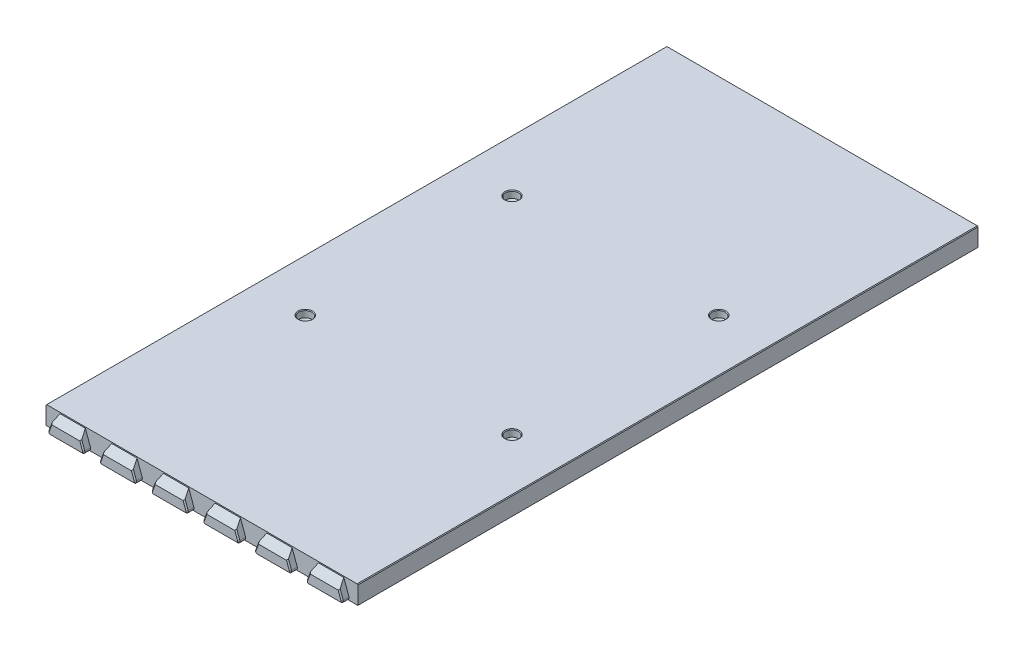
SolidWorks part; units mm, degrees
ref_plane "Front Plane" through (0, 0, 0) normal (0, 0, 1) x (1, 0, 0)
ref_plane "Top Plane" through (0, 0, 0) normal (0, 1, 0) x (1, 0, 0)
ref_plane "Right Plane" through (0, 0, 0) normal (1, 0, 0) x (0, 0, -1)
sketch "Sketch1" plane through (0, 0, 0) normal (0, 0, 1) x (1, 0, 0)
  line L0 (0, 0) -> (0, 8) construction
  line L1 (-67.875, 0) -> (0, 0) construction
  line L2 (-67.875, 0) -> (-67.875, 8)
  line L3 (-67.875, 8) -> (67.875, 8)
  line L5 (-67.875, 0) -> (-65.875, 0)
  line L6 (-65.875, 0) -> (-65.875, 6)
  line L7 (-65.875, 6) -> (65.875, 6)
  line L9 (65.875, 0) -> (65.875, 6)
  line L10 (67.875, 0) -> (65.875, 0)
  line L11 (67.875, 0) -> (67.875, 8)
  point P8 (0, 6)
  dimension "D2" = 6
  dimension "D1" = 67.875
  dimension "D3" = 2
  dimension "D4" = 2
extrude "Boss-Extrude1" add sketch "Sketch1" against normal blind 135
sketch "Sketch7" plane through (0, 0, 0) normal (0, 0, 1) x (1, 0, 0)
  line L2 (-65.875, 0) -> (65.875, 0)
  line L13 (-65.875, 0) -> (-65.875, 6)
  line L15 (-65.875, 6) -> (65.875, 6)
  line L16 (65.875, 0) -> (65.875, 6)
  line M3 (-65.875, 0) -> (-65.875, 6)
  line M4 (-65.875, 6) -> (65.875, 6)
  line M5 (65.875, 6) -> (65.875, 0)
extrude "Boss-Extrude7" add sketch "Sketch7" against normal blind 1 contours M4 M3 | M5 region at (0, 3, 0)
sketch "Sketch2" plane through (0, 0, 0) normal (0, 0, 1) x (1, 0, 0)
  line L14 (50.9118, 8) -> (48, 0)
  line L15 (67.875, 8) -> (-67.875, 8) construction
  line L16 (-67.875, 0) -> (67.875, 0) construction
  line L17 (48, 0) -> (64.5, 0)
  line L18 (50.9118, 8) -> (61.5882, 8)
  line L19 (-67.875, 0) -> (67.875, 0) construction
  line L21 (61.5882, 8) -> (64.5, 0)
  line L24 (45, 0) -> (45, 8) construction
  line L27 (28.4118, 8) -> (25.5, 0)
  line L28 (28.4118, 8) -> (39.0882, 8)
  line L29 (25.5, 0) -> (42, 0)
  line L30 (39.0882, 8) -> (42, 0)
  line L31 (5.9118, 8) -> (3, 0)
  line L32 (5.9118, 8) -> (16.5882, 8)
  line L33 (3, 0) -> (19.5, 0)
  line L34 (16.5882, 8) -> (19.5, 0)
  line L35 (-16.5882, 8) -> (-19.5, 0)
  line L36 (-16.5882, 8) -> (-5.9118, 8)
  line L37 (-19.5, 0) -> (-3, 0)
  line L38 (-5.9118, 8) -> (-3, 0)
  line L39 (50.9118, 8) -> (28.4118, 8) construction
  line L40 (67.5, 8) -> (67.5, 0) construction
  line L41 (67.875, 0) -> (67.875, 8) construction
  line L42 (-67.5, 8) -> (-67.5, 0) construction
  line L43 (-67.875, 8) -> (-67.875, 0) construction
  line L44 (-39.0882, 8) -> (-42, 0)
  line L45 (-39.0882, 8) -> (-28.4118, 8)
  line L46 (-42, 0) -> (-25.5, 0)
  line L47 (-28.4118, 8) -> (-25.5, 0)
  line L48 (-61.5882, 8) -> (-64.5, 0)
  line L49 (-61.5882, 8) -> (-50.9118, 8)
  line L50 (-64.5, 0) -> (-48, 0)
  line L51 (-50.9118, 8) -> (-48, 0)
  point P22 (56.25, 8)
  point P23 (33.75, 8)
  dimension "D1" = 70
  dimension "D2" = 0.375
  dimension "D3" = 3
  dimension "D4" = 3
  dimension "D5" = 70
  dimension "D7" = 22.5
  dimension "D8" = 22.5
  dimension "D9" = 0.375
  dimension "D10" = 48
  dimension "D11" = 8
  dimension "D6" = 6
extrude "Boss-Extrude4" add sketch "Sketch2" along normal blind 3
sketch "Sketch8" plane through (0, 0, 0) normal (0, -1, 0) x (1, 0, 0)
  line L0 (-67.875, -22.5) -> (67.875, -22.5) construction
  line L1 (-66.35, -20.2583) -> (-62.65, -21.605)
  line L2 (67.875, -135) -> (67.875, 0) construction
  line L3 (-67.875, 0) -> (-64.5, 0) construction
  line L4 (-66.5, -24.9559) -> (-66.5, -20.0441) construction
  line L5 (-66.5, -20.0441) -> (-62.5, -21.5) construction
  line L6 (-62.5, -21.5) -> (-62.5, -23.5) construction
  line L7 (-66.5, -135) -> (-66.5, -132.5441) construction
  line L8 (-66.5, -132.5441) -> (-62.5, -134) construction
  line L9 (-62.5, -134) -> (-62.5, -135) construction
  line L10 (-65.875, -135) -> (65.875, -135) construction
  line L11 (-62.5, -135) -> (-66.5, -135) construction
  line L12 (-66.5, -24.9559) -> (-62.5, -23.5) construction
  line L13 (0, -135) -> (0, 0) construction
  line L22 (-62.65, -21.605) -> (-62.65, -23.395)
  line L23 (-67.875, -135) -> (-67.875, 0) construction
  line L28 (-67.875, -135) -> (-65.875, -135) construction
  line L33 (-66.35, -24.7417) -> (-62.65, -23.395)
  line L34 (-66.35, -24.7417) -> (-66.35, -20.2583)
  line L35 (-66.35, -132.7583) -> (-62.65, -134.105)
  line L36 (-62.65, -134.105) -> (-62.65, -134.85)
  line L37 (-62.65, -134.85) -> (-66.35, -134.85) construction
  line L38 (-66.35, -134.85) -> (-66.35, -132.7583)
  line L39 (-66.35, -134.85) -> (-66.35, -135)
  line L40 (-66.35, -135) -> (-62.65, -135)
  line L41 (-62.65, -135) -> (-62.65, -134.85)
  line L42 (66.35, -24.7417) -> (66.35, -20.2583)
  line L43 (66.35, -24.7417) -> (62.65, -23.395)
  line L44 (62.65, -21.605) -> (62.65, -23.395)
  line L45 (66.35, -20.2583) -> (62.65, -21.605)
  line L46 (66.35, -135) -> (62.65, -135)
  line L47 (66.35, -134.85) -> (66.35, -135)
  line L48 (66.35, -134.85) -> (66.35, -132.7583)
  line L49 (66.35, -132.7583) -> (62.65, -134.105)
  line L50 (62.65, -134.105) -> (62.65, -134.85)
  line L51 (62.65, -135) -> (62.65, -134.85)
  point P19 (-62.5, -22.5)
  dimension "D1" = 22.5
  dimension "D2" = 0.15
  dimension "D3" = 70
  dimension "D4" = 4
  dimension "D5" = 1.375
  dimension "D6" = 4
  dimension "D7" = 70
  dimension "D8" = 1
  dimension "D9" = 1
  dimension "D10" = 0.15
extrude "Boss-Extrude8" add sketch "Sketch8" against normal up to next and the other way blind 2
chamfer "Chamfer4" distance 0.5 angle 45 14 edges at (-64.5, -2, -133.4317) (-62.65, -2, -134.5525) (-66.35, -2, -133.8792) (62.65, -2, -22.5) (64.5, -2, -20.9317) (66.35, -2, -22.5) (64.5, -2, -24.0683) (-64.5, -2, -20.9317) (-62.65, -2, -22.5) (-64.5, -2, -24.0683) (-66.35, -2, -22.5) (62.65, -2, -134.5525) (64.5, -2, -133.4317) (66.35, -2, -133.8792)
fillet "Fillet4" radius 1 12 edges at (64.5, 0, 1.5) (48, 0, 1.5) (42, 0, 1.5) (25.5, 0, 1.5) (19.5, 0, 1.5) (3, 0, 1.5) (-3, 0, 1.5) (-19.5, 0, 1.5) (-25.5, 0, 1.5) (-42, 0, 1.5) (-48, 0, 1.5) (-64.5, 0, 1.5)
chamfer "Chamfer6" distance 0.5 angle 45 30 edges at (49.7001, 4.671, 3) (62.7999, 4.671, 3) (56.25, 0, 3) (-17.7999, 4.671, 3) (-11.25, 0, 3) (-4.7001, 4.671, 3) (4.7001, 4.671, 3) (11.25, 0, 3) (17.7999, 4.671, 3) (27.2001, 4.671, 3) (40.2999, 4.671, 3) (33.75, 0, 3) (-40.2999, 4.671, 3) (-27.2001, 4.671, 3) (-33.75, 0, 3) (-62.7999, 4.671, 3) (-49.7001, 4.671, 3) (-56.25, 0, 3) (-63.891, 0.4264, 3) (-48.609, 0.4264, 3) (-41.391, 0.4264, 3) (-26.109, 0.4264, 3) (-18.891, 0.4264, 3) (-3.609, 0.4264, 3) (3.609, 0.4264, 3) (18.891, 0.4264, 3) (26.109, 0.4264, 3) (41.391, 0.4264, 3) (48.609, 0.4264, 3) (63.891, 0.4264, 3)
fillet "Fillet2" radius 2 23 edges at (0, 6, -1) (-65.875, 3, -1) (65.875, 6, -10.7156) (65.875, 3, -1) (-65.875, 6, -10.7156) (62.65, 6, -22.5) (64.2625, 6, -21.0181) (65.875, 3, -20.4312) (65.875, 3, -24.5688) (64.2625, 6, -23.9819) (65.875, 6, -78.75) (65.875, 3, -132.9312) (64.2625, 6, -133.5181) (62.65, 6, -134.5525) (-62.65, 6, -134.5525) (-64.2625, 6, -133.5181) (-65.875, 3, -132.9312) (-65.875, 3, -20.4312) (-64.2625, 6, -21.0181) (-62.65, 6, -22.5) (-64.2625, 6, -23.9819) (-65.875, 6, -78.75) (-65.875, 3, -24.5688)
mirror "Mirror2" about plane through (0, 0, -135) normal (0, 0, 1) of "Fillet4", "Boss-Extrude1", "Boss-Extrude7", "Boss-Extrude4", "Boss-Extrude8", "Chamfer4", "Fillet2", "Chamfer6"
sketch "Sketch9" plane through (0, 0, 0) normal (0, 1, 0) x (1, 0, 0)
  line L16 (0, 135) -> (0, 0) construction
  line L17 (-67.875, 135) -> (67.875, 135) construction
  line L20 (67.875, 270) -> (67.875, 0) construction
  line L21 (-67.875, 270) -> (-67.875, 0) construction
  circle A0 centre (-45, 90) radius 5
  circle A4 centre (45, 90) radius 5
  circle A5 centre (45, 180) radius 5
  circle A6 centre (-45, 180) radius 5
  point P23 (0, 135)
  point P24 (0, 135)
  dimension "D3" = 10
  dimension "D1" = 45
  dimension "D2" = 45
extrude "Boss-Extrude9" add sketch "Sketch9" along normal up to next
fillet "Fillet3" radius 3 4 edges at (-45, 6, -95) (45, 6, -185) (-45, 6, -185) (45, 6, -95)
sketch "Sketch10" plane through (0, 0, 0) normal (0, 1, 0) x (1, 0, 0)
  circle A0 centre (-45, 180) radius 1.85
  circle A1 centre (-45, 90) radius 1.85
  circle A2 centre (45, 90) radius 1.85
  circle A3 centre (45, 180) radius 1.85
  dimension "D1" = 3.7
extrude "Cut-Extrude2" cut sketch "Sketch10" along normal through all
sketch "Sketch11" plane through (0, 8, 0) normal (0, 1, 0) x (1, 0, 0)
  circle A0 centre (-45, 180) radius 2.85
  circle A1 centre (45, 180) radius 2.85
  circle A2 centre (45, 90) radius 2.85
  circle A3 centre (-45, 90) radius 2.85
  dimension "D1" = 5.7
extrude "Cut-Extrude3" cut sketch "Sketch11" against normal blind 3
chamfer "Chamfer7" distance 1 angle 45 4 edges at (45, 5, -178.15) (-45, 5, -178.15) (45, 5, -88.15) (-45, 5, -88.15)
sketch "Sketch12" plane through (0, 0, 0) normal (1, 0, 0) x (0, 0, -1)
  line L0 (0, 7.5) -> (-3, 4.5)
  line L1 (-3, 1.171) -> (-3, 8) construction
  line L2 (-3, 4.5) -> (-3, 7.5)
  line L3 (-3, 7.5) -> (0, 7.5) construction
  line L4 (135, 8) -> (135, 0) construction
  line L5 (270, 8) -> (0, 8) construction
  line L6 (270, 0) -> (0, 0) construction
  line L10 (0, 0) -> (0, 8) construction
  line L11 (0, 7.5) -> (0, 8)
  line L12 (0, 8) -> (-3, 8)
  line L13 (-3, 8) -> (-3, 7.5)
  line L14 (273, 7.5) -> (270, 7.5) construction
  line L15 (273, 8) -> (273, 7.5)
  line L16 (270, 8) -> (273, 8)
  line L17 (270, 7.5) -> (270, 8)
  line L18 (273, 4.5) -> (273, 7.5)
  line L19 (270, 7.5) -> (273, 4.5)
  dimension "D1" = 45
  dimension "D2" = 3
  dimension "D3" = 0.5
extrude "Cut-Extrude4" cut sketch "Sketch12" against normal through all both and the other way through all
chamfer "Chamfer8" distance 0.3 angle 45 6 edges at (67.875, 8, -135) (-67.875, 8, -135) (-45, 8, -177.15) (-45, 8, -87.15) (45, 8, -87.15) (45, 8, -177.15)
